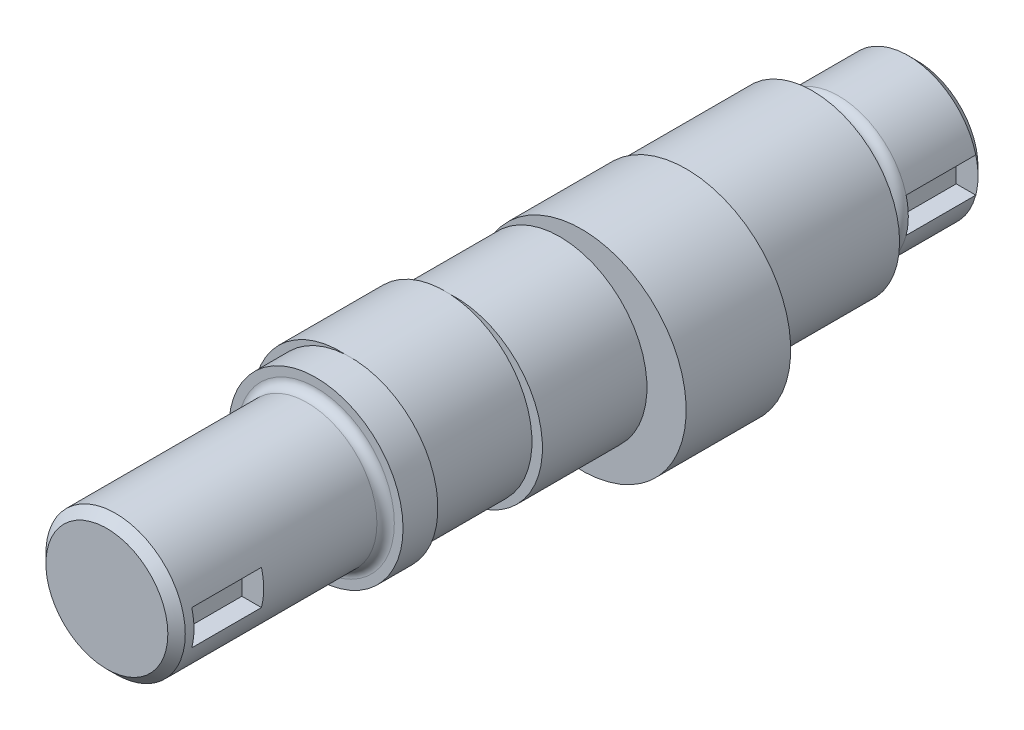
SolidWorks part; units mm, degrees
ref_plane "前视基准面" through (0, 0, 0) normal (0, 0, 1) x (1, 0, 0)
ref_plane "上视基准面" through (0, 0, 0) normal (0, 1, 0) x (1, 0, 0)
ref_plane "右视基准面" through (0, 0, 0) normal (1, 0, 0) x (0, 0, -1)
other "Configuration Table"
ref_plane "P_zm13" through (0, 0, -13) normal (0, 0, 1) x (1, 0, 0)
sketch "草图1" plane through (0, 0, -13) normal (0, 0, 1) x (1, 0, 0)
  circle A0 centre (0, 0) radius 8
extrude "凸台-拉伸1" add sketch "草图1" along normal blind 10
ref_plane "P_zm3" through (0, 0, -3) normal (0, 0, 1) x (1, 0, 0)
sketch "草图2" plane through (0, 0, -3) normal (0, 0, 1) x (1, 0, 0)
  circle A0 centre (0, 0) radius 6.5
extrude "凸台-拉伸2" add sketch "草图2" along normal blind 2
ref_plane "P_zm1" through (0, 0, -1) normal (0, 0, 1) x (1, 0, 0)
sketch "草图3" plane through (0, 0, -1) normal (0, 0, 1) x (1, 0, 0)
  circle A0 centre (0, 0) radius 10
extrude "凸台-拉伸3" add sketch "草图3" along normal blind 17
ref_plane "P_z16" through (0, 0, 16) normal (0, 0, 1) x (1, 0, 0)
sketch "草图4" plane through (0, 0, 16) normal (0, 0, 1) x (1, 0, 0)
  circle A0 centre (2.5, 0) radius 12
extrude "凸台-拉伸4" add sketch "草图4" along normal blind 12
ref_plane "P_z28" through (0, 0, 28) normal (0, 0, 1) x (1, 0, 0)
sketch "草图5" plane through (0, 0, 28) normal (0, 0, 1) x (1, 0, 0)
  circle A0 centre (0, 0) radius 10
extrude "凸台-拉伸5" add sketch "草图5" along normal blind 12
ref_plane "P_z40" through (0, 0, 40) normal (0, 0, 1) x (1, 0, 0)
sketch "草图6" plane through (0, 0, 40) normal (0, 0, 1) x (1, 0, 0)
  circle A0 centre (-1.2, 0) radius 10
extrude "凸台-拉伸6" add sketch "草图6" along normal blind 12
ref_plane "P_z52" through (0, 0, 52) normal (0, 0, 1) x (1, 0, 0)
sketch "草图7" plane through (0, 0, 52) normal (0, 0, 1) x (1, 0, 0)
  circle A0 centre (0, 0) radius 10
extrude "凸台-拉伸7" add sketch "草图7" along normal blind 4
ref_plane "P_z56" through (0, 0, 56) normal (0, 0, 1) x (1, 0, 0)
sketch "草图8" plane through (0, 0, 56) normal (0, 0, 1) x (1, 0, 0)
  circle A0 centre (0, 0) radius 8
extrude "凸台-拉伸8" add sketch "草图8" along normal blind 24
ref_plane "P_zm12" through (0, 0, -12) normal (0, 0, 1) x (1, 0, 0)
sketch "草图9" plane through (0, 0, -12) normal (0, 0, 1) x (1, 0, 0)
  line L1 (5.5, -2) -> (11, -2)
  line L2 (5.5, -2) -> (5.5, 2)
  line L3 (5.5, 2) -> (11, 2)
  line L4 (11, -2) -> (11, 2)
extrude "切除-拉伸1" cut sketch "草图9" along normal blind 8
ref_plane "P_z70" through (0, 0, 70) normal (0, 0, 1) x (1, 0, 0)
sketch "草图10" plane through (0, 0, 70) normal (0, 0, 1) x (1, 0, 0)
  line L1 (5.5, -2) -> (11, -2)
  line L2 (5.5, -2) -> (5.5, 2)
  line L3 (5.5, 2) -> (11, 2)
  line L4 (11, -2) -> (11, 2)
extrude "切除-拉伸2" cut sketch "草图10" along normal blind 8
chamfer "倒角1" distance 1 angle 45 2 edges at (8, 0, 80) (8, 0, -13)
fillet "圆角1" radius 1 3 edges at (8, 0, 56) (8, 0, -3) (6.5, 0, -1)
